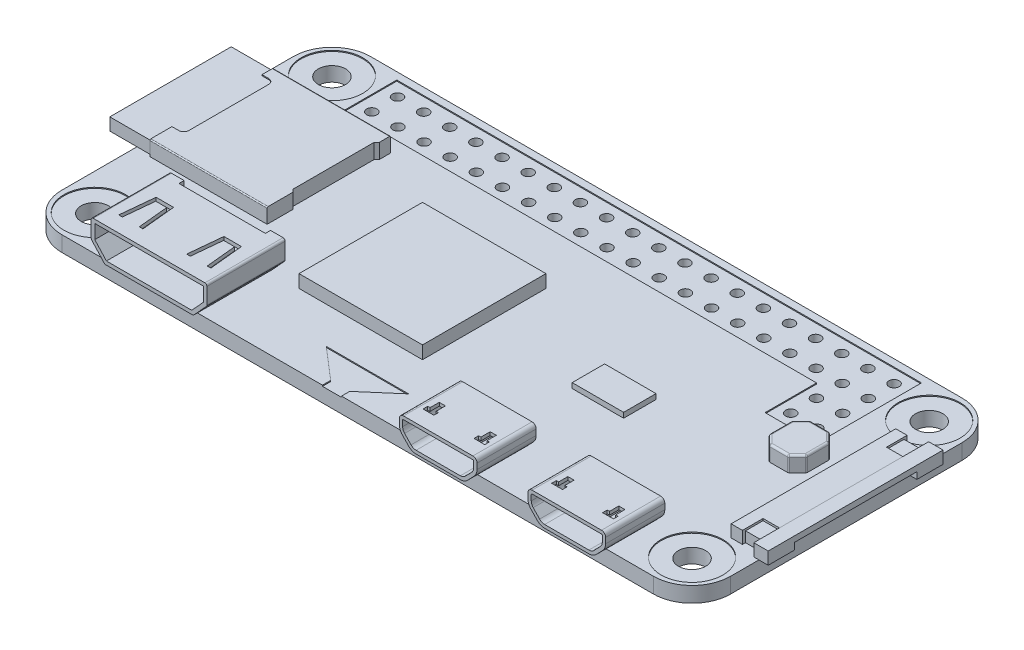
SolidWorks part; units mm, degrees
ref_plane "Front Plane" through (0, 0, 0) normal (0, 0, 1) x (1, 0, 0)
ref_plane "Top Plane" through (0, 0, 0) normal (0, 1, 0) x (1, 0, 0)
ref_plane "Right Plane" through (0, 0, 0) normal (1, 0, 0) x (0, 0, -1)
sketch "Sketch1" plane through (0, 0, 0) normal (0, 1, 0) x (1, 0, 0)
  line L1 (-28.75, 15) -> (28.75, 15)
  line L2 (-32.5, 11.25) -> (-32.5, -11.25)
  line L3 (-28.75, -15) -> (28.75, -15)
  line L4 (32.5, 11.25) -> (32.5, -11.25)
  line L5 (-32.5, 15) -> (32.5, -15) construction
  line L6 (-32.5, -15) -> (32.5, 15) construction
  arc A0 (-32.5, -11.25) -> (-28.75, -15) centre (-28.75, -11.25) ccw
  arc A1 (28.75, -15) -> (32.5, -11.25) centre (28.75, -11.25) ccw
  arc A2 (28.75, 15) -> (32.5, 11.25) centre (28.75, 11.25) cw
  arc A3 (-28.75, 15) -> (-32.5, 11.25) centre (-28.75, 11.25) ccw
  point P0 (0, 0)
  dimension "D3" = 3.75
  dimension "D1" = 65
  dimension "D2" = 30
extrude "Boss-Extrude1" add sketch "Sketch1" along normal blind 1.5 contours L1 A2 L4 A1 L3 A0 L2 A3
sketch "Sketch2" plane through (0, 1.5, 0) normal (0, 1, 0) x (1, 0, 0)
  line L0 (0, 15) -> (0, -15) construction
  line L1 (-28.75, 15) -> (28.75, 15) construction
  line L2 (-28.75, -15) -> (28.75, -15) construction
  line L3 (-32.5, 0) -> (32.5, 0) construction
  line L4 (-32.5, 11.25) -> (-32.5, -11.25) construction
  line L5 (32.5, 11.25) -> (32.5, -11.25) construction
  circle A0 centre (-29.025, 11.525) radius 1.325
  circle A2 centre (29.025, 11.525) radius 1.325
  circle A3 centre (29.025, -11.525) radius 1.325
  circle A4 centre (-29.025, -11.525) radius 1.325
  dimension "D1" = 2.65
  dimension "D2" = 2.15
  dimension "D3" = 2.15
extrude "Cut-Extrude1" cut sketch "Sketch2" against normal through all
sketch "Sketch3" plane through (0, 1.5, 0) normal (0, 1, 0) x (1, 0, 0)
  line L0 (-24.128, 13) -> (-24.128, 10.5) construction
  line L3 (-28.75, 15) -> (28.75, 15) construction
  line L5 (-32.5, 11.25) -> (-32.5, -11.25) construction
  circle A0 centre (-24.128, 13) radius 0.5
  circle A1 centre (-24.128, 10.5) radius 0.5
  dimension "D1" = 1
  dimension "D3" = 1.5
  dimension "D4" = 7.872
  dimension "D2" = 2.5
extrude "Cut-Extrude2" cut sketch "Sketch3" against normal through all
pattern_linear "LPattern1" count 20 spacing 2.54 along (1, 0, 0) of "Cut-Extrude2"
sketch "Sketch5" plane through (0, 1.5, 0) normal (0, 1, 0) x (1, 0, 0)
  line L0 (21.592, 10.5) -> (21.592, 5.5) construction
  line L1 (24.132, 10.5) -> (24.132, 5.5) construction
  line L2 (24.132, 5.5) -> (21.592, 5.5) construction
  circle A0 centre (21.592, 5.5) radius 0.5
  circle A1 centre (24.132, 5.5) radius 0.5
  circle A2 centre (21.592, 8) radius 0.5
  circle A3 centre (24.132, 8) radius 0.5
  dimension "D1" = 2.5
  dimension "D2" = 1
extrude "Cut-Extrude4" cut sketch "Sketch5" against normal through all
sketch "Sketch4" plane through (0, 1.5, 0) normal (0, 1, 0) x (1, 0, 0)
  line L0 (0, 0) -> (0, 14.3) construction
  line L1 (-24.128, 13) -> (-24.128, 10.5) construction
  line L2 (-25.5, 14.3) -> (25.5, 14.3)
  line L3 (-25.5, 14.3) -> (-25.5, 9.2)
  line L4 (-25.5, 9.2) -> (20.4, 9.2)
  line L5 (25.5, 14.3) -> (25.5, 9.2)
  line L6 (-25.5, 11.75) -> (-24.128, 11.75) construction
  line L7 (20.4, 9.2) -> (25.5, 9.2) construction
  line L8 (-2.5, -15) -> (-2.5, -11.55) construction
  line L9 (25.5, 9.2) -> (25.5, 4.2)
  line L10 (25.5, 4.2) -> (20.4, 4.2)
  line L11 (20.4, 9.2) -> (20.4, 4.2)
  line L12 (-28.75, -15) -> (28.75, -15) construction
  line L13 (-6.5, -11.55) -> (1.5, -11.55)
  line L14 (1.5, -11.55) -> (-1.575, -14.2)
  line L15 (-1.575, -14.2) -> (-1.575, -15)
  line L16 (-1.575, -15) -> (-3.425, -15)
  line L17 (-3.425, -15) -> (-3.425, -14.2)
  line L18 (-3.425, -14.2) -> (-6.5, -11.55)
  line L19 (-32.5, 11.25) -> (-32.5, -11.25) construction
  circle A0 centre (-29.025, 11.525) radius 3
  circle A1 centre (-29.025, -11.525) radius 3
  circle A2 centre (29.025, -11.525) radius 3
  circle A3 centre (29.025, 11.525) radius 3
  point P23 (-24.128, 11.75)
  point P26 (-25.5, 11.75)
  dimension "D1" = 6
  dimension "D2" = 5.1
  dimension "D3" = 51
  dimension "D4" = 5.1
  dimension "D5" = 5
  dimension "D6" = 8
  dimension "D7" = 1.85
  dimension "D8" = 3.45
  dimension "D9" = 0.8
  dimension "D10" = 30
extrude "Cut-Extrude3" cut sketch "Sketch4" against normal blind 0.1
sketch "Sketch6" plane through (0, 1.5, 0) normal (0, 1, 0) x (1, 0, 0)
  line L0 (-28.75, -15) -> (-3.425, -15) construction
  line L1 (-12.7, 4) -> (-0.7, 4)
  line L2 (-12.7, 4) -> (-12.7, -8)
  line L3 (-12.7, -8) -> (-0.7, -8)
  line L4 (-0.7, 4) -> (-0.7, -8)
  line L5 (-12.7, 4) -> (-0.7, -8) construction
  line L6 (-12.7, -8) -> (-0.7, 4) construction
  line L7 (-32.5, 11.25) -> (-32.5, -11.25) construction
  point P0 (-6.7, -2)
  dimension "D1" = 12
  dimension "D2" = 7
  dimension "D3" = 19.8
extrude "Boss-Extrude2" add sketch "Sketch6" along normal blind 1.25
sketch "Sketch7" plane through (0, 1.5, 0) normal (0, 1, 0) x (1, 0, 0)
  line L0 (-19.65, 7.85) -> (-19.65, 6.75)
  line L1 (-31.05, 7.85) -> (-19.65, 7.85)
  line L2 (-31.05, 7.85) -> (-31.05, -4.15) construction
  line L3 (-31.05, -4.15) -> (-19.65, -4.15)
  line L4 (-19.65, 7.85) -> (-19.65, -4.15) construction
  line L5 (-19.65, 6.75) -> (-19.9, 6.5)
  line L6 (-19.9, 6.5) -> (-19.9, -1.4)
  line L7 (-19.9, -1.4) -> (-19.65, -1.65)
  line L8 (-19.65, -1.65) -> (-19.65, -4.15)
  line L9 (-31.05, 7.85) -> (-31.05, 6.75)
  line L10 (-31.05, 6.75) -> (-30.4, 6.75)
  line L11 (-29.9, 6.25) -> (-29.9, -1.5)
  line L12 (-30.4, -2) -> (-31.05, -2)
  line L13 (-31.05, -2) -> (-31.05, -4.15)
  line L14 (-28.75, 15) -> (28.75, 15) construction
  line L15 (-32.5, 11.25) -> (-32.5, -11.25) construction
  arc A0 (-29.9, -1.5) -> (-30.4, -2) centre (-30.4, -1.5) cw
  arc A1 (-30.4, 6.75) -> (-29.9, 6.25) centre (-30.4, 6.25) cw
  dimension "D9" = 0.5
  dimension "D1" = 11.4
  dimension "D2" = 12
  dimension "D3" = 2.5
  dimension "D4" = 1.1
  dimension "D5" = 0.25
  dimension "D6" = 1.1
  dimension "D7" = 2.15
  dimension "D8" = 1.15
  dimension "D10" = 7.15
  dimension "D11" = 1.45
extrude "Boss-Extrude3" add sketch "Sketch7" along normal blind 1.45
fillet "Fillet2" radius 0.1 2 edges at (-25.35, 2.95, -7.85) (-25.35, 2.95, 4.15)
sketch "Sketch8" plane through (-29.9, 0, 0) normal (-1, 0, 0) x (0, 0, 1)
  line L0 (-7.85, 2.85) -> (-7.85, 1.5) construction
  line L1 (-7.75, 2.85) -> (4.05, 2.85)
  line L2 (-7.75, 2.85) -> (-7.75, 1.6)
  line L3 (-7.75, 1.6) -> (4.05, 1.6)
  line L4 (4.05, 2.85) -> (4.05, 1.6)
  line L5 (-6.25, 2.95) -> (1.5, 2.95) construction
  line L6 (4.15, 2.85) -> (4.15, 1.5) construction
  line L7 (-6.25, 1.5) -> (1.5, 1.5) construction
  dimension "D1" = 0.1
  dimension "D2" = 0.1
  dimension "D3" = 0.1
  dimension "D4" = 0.1
extrude "Cut-Extrude5" cut sketch "Sketch8" against normal blind 9.5 and the other way through all
sketch "Sketch9" plane through (0, 0, 15) normal (0, 0, 1) x (1, 0, 0)
  line L0 (-19.875, 1.5) -> (-19.875, 4.8) construction
  line L1 (-28.75, 1.5) -> (-3.425, 1.5) construction
  line L2 (-25.5, 4.8) -> (-14.25, 4.8)
  line L3 (-14.25, 4.8) -> (-14.25, 2.95)
  line L4 (-14.25, 2.95) -> (-15.575, 1.5)
  line L5 (-12.7, 1.5) -> (-0.7, 1.5) construction
  line L6 (-15.575, 1.5) -> (-24.175, 1.5)
  line L7 (-24.175, 1.5) -> (-25.5, 2.95)
  line L8 (-25.5, 2.95) -> (-25.5, 4.8)
  line L9 (-32.5, 1.5) -> (-32.5, 0) construction
  dimension "D1" = 3.3
  dimension "D2" = 1.85
  dimension "D3" = 8.6
  dimension "D4" = 11.25
  dimension "D5" = 7
extrude "Boss-Extrude4" add sketch "Sketch9" along normal blind 0.4 and the other way blind 7.2 separate body
fillet "Fillet1" radius 0.2 6 edges at (-15.575, 1.5, 11.6) (-24.175, 1.5, 11.6) (-25.5, 2.95, 11.6) (-14.25, 2.95, 11.6) (-25.5, 4.8, 11.6) (-14.25, 4.8, 11.6)
sketch "Sketch10" plane through (0, 0, 15.4) normal (0, 0, 1) x (1, 0, 0)
  line L12 (-25.15, 4.45) -> (-25.15, 3.0858)
  line L13 (-25.15, 3.0858) -> (-24.0207, 1.85)
  line L14 (-24.0207, 1.85) -> (-15.7293, 1.85)
  line L15 (-15.7293, 1.85) -> (-14.6, 3.0858)
  line L16 (-14.6, 3.0858) -> (-14.6, 4.45)
  line L17 (-14.6, 4.45) -> (-25.15, 4.45)
  line L18 (-25.15, 4.45) -> (-25.15, 3.0858)
  line L19 (-25.15, 3.0858) -> (-24.0207, 1.85)
  line L20 (-24.0207, 1.85) -> (-15.7293, 1.85)
  line L21 (-15.7293, 1.85) -> (-14.6, 3.0858)
  line L22 (-14.6, 3.0858) -> (-14.6, 4.45)
  line L23 (-14.6, 4.45) -> (-25.15, 4.45)
  dimension "D1" = 0.35
extrude "Cut-Extrude6" cut sketch "Sketch10" against normal blind 7
sketch "Sketch11" plane through (0, 0, 8.4) normal (0, 0, 1) x (1, 0, 0)
  line L0 (-19.875, 3.6) -> (-19.875, 1.85) construction
  line L1 (-23.375, 3.05) -> (-16.375, 3.05)
  line L2 (-23.375, 3.05) -> (-23.375, 3.6)
  line L3 (-23.375, 3.6) -> (-16.375, 3.6)
  line L4 (-16.375, 3.05) -> (-16.375, 3.6)
  line L5 (-24.0207, 1.85) -> (-15.7293, 1.85) construction
  line L6 (-24.0207, 1.85) -> (-15.7293, 1.85) construction
  dimension "D1" = 7
  dimension "D2" = 0.55
  dimension "D3" = 1.2
extrude "Boss-Extrude5" add sketch "Sketch11" along normal blind 3.5
sketch "Sketch12" plane through (0, 4.45, 0) normal (0, -1, 0) x (1, 0, 0)
  line L0 (-19.875, 7.8) -> (-19.875, 15.4) construction
  line L1 (-14.45, 7.8) -> (-25.3, 7.8) construction
  line L2 (-14.45, 15.4) -> (-25.3, 15.4) construction
  line L3 (-23.175, 10.57) -> (-23.175, 13.4458) construction
  line L4 (-24.025, 10.57) -> (-22.325, 10.57)
  line L5 (-22.325, 10.57) -> (-22, 13.87)
  line L6 (-22, 13.87) -> (-22.3517, 13.87)
  line L7 (-22.3517, 13.87) -> (-22.6422, 10.92)
  line L8 (-22.6422, 10.92) -> (-23.7078, 10.92)
  line L9 (-23.9983, 13.87) -> (-23.7078, 10.92)
  line L10 (-24.35, 13.87) -> (-23.9983, 13.87)
  line L11 (-24.025, 10.57) -> (-24.35, 13.87)
  line L12 (-16.575, 10.57) -> (-16.575, 13.4458) construction
  line L13 (-15.725, 10.57) -> (-15.4, 13.87)
  line L14 (-15.4, 13.87) -> (-15.7517, 13.87)
  line L15 (-15.7517, 13.87) -> (-16.0422, 10.92)
  line L16 (-17.1078, 10.92) -> (-16.0422, 10.92)
  line L17 (-17.3983, 13.87) -> (-17.1078, 10.92)
  line L18 (-17.75, 13.87) -> (-17.3983, 13.87)
  line L19 (-17.425, 10.57) -> (-17.75, 13.87)
  line L20 (-15.725, 10.57) -> (-17.425, 10.57)
  point P15 (-23.175, 10.92)
  point P28 (-16.575, 10.92)
  dimension "D1" = 0.35
  dimension "D2" = 0.35
  dimension "D3" = 3.3
  dimension "D4" = 2.35
  dimension "D5" = 1.7
  dimension "D6" = 2.77
  dimension "D7" = 4.25
extrude "Cut-Extrude7" cut sketch "Sketch12" against normal through all
sketch "Sketch13" plane through (0, 0, 7.8) normal (0, 0, -1) x (-1, 0, 0)
  line L0 (14.45, 4.8) -> (25.3, 4.8) construction
  line L1 (15.675, 4.8) -> (24.075, 4.8)
  line L2 (15.675, 4.8) -> (15.675, 3.4)
  line L3 (15.675, 3.4) -> (24.075, 3.4)
  line L4 (24.075, 4.8) -> (24.075, 3.4)
  line L5 (19.875, 1.5) -> (19.875, 4.8) construction
  line L6 (24.0868, 1.5) -> (15.6632, 1.5) construction
  dimension "D1" = 8.4
  dimension "D2" = 1.4
extrude "Cut-Extrude8" cut sketch "Sketch13" against normal blind 0.5
sketch "Sketch15" plane through (0, 0, 15) normal (0, 0, 1) x (1, 0, 0)
  line L0 (21.575, 1.5) -> (21.575, 4.1) construction
  line L1 (-1.575, 1.5) -> (28.75, 1.5) construction
  line L2 (18.2, 4.1) -> (24.95, 4.1)
  line L3 (25.35, 3.7) -> (25.35, 3.1523)
  line L4 (25.0714, 2.4598) -> (24.4452, 1.8075)
  line L5 (23.7238, 1.5) -> (19.4262, 1.5)
  line L6 (32.5, 1.5) -> (32.5, 0) construction
  line L7 (18.0786, 2.4598) -> (18.7048, 1.8075)
  line L8 (17.8, 3.7) -> (17.8, 3.1523)
  line L9 (15.325, 0) -> (15.325, 5.5788) construction
  line L10 (-28.75, 0) -> (28.75, 0) construction
  line L11 (9.075, 1.5) -> (9.075, 4.1) construction
  line L12 (12.85, 3.7) -> (12.85, 3.1523)
  line L13 (12.5714, 2.4598) -> (11.9452, 1.8075)
  line L14 (6.9262, 1.5) -> (11.2238, 1.5)
  line L15 (5.5786, 2.4598) -> (6.2048, 1.8075)
  line L16 (5.3, 3.7) -> (5.3, 3.1523)
  line L17 (12.45, 4.1) -> (5.7, 4.1)
  arc A0 (24.4452, 1.8075) -> (23.7238, 1.5) centre (23.7238, 2.5) cw
  arc A1 (18.7048, 1.8075) -> (19.4262, 1.5) centre (19.4262, 2.5) ccw
  arc A2 (25.35, 3.1523) -> (25.0714, 2.4598) centre (24.35, 3.1523) cw
  arc A3 (18.0786, 2.4598) -> (17.8, 3.1523) centre (18.8, 3.1523) cw
  arc A4 (24.95, 4.1) -> (25.35, 3.7) centre (24.95, 3.7) cw
  arc A5 (17.8, 3.7) -> (18.2, 4.1) centre (18.2, 3.7) cw
  arc A6 (12.85, 3.7) -> (12.45, 4.1) centre (12.45, 3.7) ccw
  arc A7 (5.7, 4.1) -> (5.3, 3.7) centre (5.7, 3.7) ccw
  arc A8 (12.5714, 2.4598) -> (12.85, 3.1523) centre (11.85, 3.1523) ccw
  arc A9 (5.3, 3.1523) -> (5.5786, 2.4598) centre (6.3, 3.1523) ccw
  arc A10 (11.9452, 1.8075) -> (11.2238, 1.5) centre (11.2238, 2.5) cw
  arc A11 (6.2048, 1.8075) -> (6.9262, 1.5) centre (6.9262, 2.5) ccw
  point P14 (24.15, 1.5)
  point P17 (19, 1.5)
  point P20 (25.35, 2.75)
  point P23 (17.8, 2.75)
  point P26 (25.35, 4.1)
  point P29 (17.8, 4.1)
  point P54 (12.85, 4.1)
  point P55 (5.3, 4.1)
  point P56 (12.85, 2.75)
  point P57 (5.3, 2.75)
  point P58 (11.65, 1.5)
  point P59 (6.5, 1.5)
  dimension "D6" = 1
  dimension "D7" = 0.4
  dimension "D1" = 7.55
  dimension "D2" = 2.6
  dimension "D3" = 1.35
  dimension "D4" = 5.15
  dimension "D5" = 7.15
  dimension "D8" = 4.95
extrude "Boss-Extrude6" add sketch "Sketch15" along normal blind 1.25 and the other way blind 4.5
sketch "Sketch16" plane through (0, 0, 16.25) normal (0, 0, 1) x (1, 0, 0)
  line L12 (12.45, 3.78) -> (5.7, 3.78)
  line L13 (5.62, 3.7) -> (5.62, 3.1523)
  line L14 (5.8095, 2.6814) -> (6.4357, 2.0291)
  line L15 (6.9262, 1.82) -> (11.2238, 1.82)
  line L16 (11.7143, 2.0291) -> (12.3405, 2.6814)
  line L17 (12.53, 3.1523) -> (12.53, 3.7)
  line L18 (12.45, 3.78) -> (5.7, 3.78)
  line L19 (5.62, 3.7) -> (5.62, 3.1523)
  line L20 (5.8095, 2.6814) -> (6.4357, 2.0291)
  line L21 (6.9262, 1.82) -> (11.2238, 1.82)
  line L22 (11.7143, 2.0291) -> (12.3405, 2.6814)
  line L23 (12.53, 3.1523) -> (12.53, 3.7)
  line L30 (24.2143, 2.0291) -> (24.8405, 2.6814)
  line L31 (25.03, 3.1523) -> (25.03, 3.7)
  line L32 (24.95, 3.78) -> (18.2, 3.78)
  line L33 (18.12, 3.7) -> (18.12, 3.1523)
  line L34 (18.3095, 2.6814) -> (18.9357, 2.0291)
  line L35 (19.4262, 1.82) -> (23.7238, 1.82)
  line L36 (24.2143, 2.0291) -> (24.8405, 2.6814)
  line L37 (25.03, 3.1523) -> (25.03, 3.7)
  line L38 (24.95, 3.78) -> (18.2, 3.78)
  line L39 (18.12, 3.7) -> (18.12, 3.1523)
  line L40 (18.3095, 2.6814) -> (18.9357, 2.0291)
  line L41 (19.4262, 1.82) -> (23.7238, 1.82)
  arc A12 (12.53, 3.7) -> (12.45, 3.78) centre (12.45, 3.7) ccw
  arc A13 (5.7, 3.78) -> (5.62, 3.7) centre (5.7, 3.7) ccw
  arc A14 (5.62, 3.1523) -> (5.8095, 2.6814) centre (6.3, 3.1523) ccw
  arc A15 (6.4357, 2.0291) -> (6.9262, 1.82) centre (6.9262, 2.5) ccw
  arc A16 (11.2238, 1.82) -> (11.7143, 2.0291) centre (11.2238, 2.5) ccw
  arc A17 (12.3405, 2.6814) -> (12.53, 3.1523) centre (11.85, 3.1523) ccw
  arc A18 (12.53, 3.7) -> (12.45, 3.78) centre (12.45, 3.7) ccw
  arc A19 (5.7, 3.78) -> (5.62, 3.7) centre (5.7, 3.7) ccw
  arc A20 (5.62, 3.1523) -> (5.8095, 2.6814) centre (6.3, 3.1523) ccw
  arc A21 (6.4357, 2.0291) -> (6.9262, 1.82) centre (6.9262, 2.5) ccw
  arc A22 (11.2238, 1.82) -> (11.7143, 2.0291) centre (11.2238, 2.5) ccw
  arc A23 (12.3405, 2.6814) -> (12.53, 3.1523) centre (11.85, 3.1523) ccw
  arc A30 (23.7238, 1.82) -> (24.2143, 2.0291) centre (23.7238, 2.5) ccw
  arc A31 (24.8405, 2.6814) -> (25.03, 3.1523) centre (24.35, 3.1523) ccw
  arc A32 (25.03, 3.7) -> (24.95, 3.78) centre (24.95, 3.7) ccw
  arc A33 (18.2, 3.78) -> (18.12, 3.7) centre (18.2, 3.7) ccw
  arc A34 (18.12, 3.1523) -> (18.3095, 2.6814) centre (18.8, 3.1523) ccw
  arc A35 (18.9357, 2.0291) -> (19.4262, 1.82) centre (19.4262, 2.5) ccw
  arc A36 (23.7238, 1.82) -> (24.2143, 2.0291) centre (23.7238, 2.5) ccw
  arc A37 (24.8405, 2.6814) -> (25.03, 3.1523) centre (24.35, 3.1523) ccw
  arc A38 (25.03, 3.7) -> (24.95, 3.78) centre (24.95, 3.7) ccw
  arc A39 (18.2, 3.78) -> (18.12, 3.7) centre (18.2, 3.7) ccw
  arc A40 (18.12, 3.1523) -> (18.3095, 2.6814) centre (18.8, 3.1523) ccw
  arc A41 (18.9357, 2.0291) -> (19.4262, 1.82) centre (19.4262, 2.5) ccw
  dimension "D1" = 0.32
  dimension "D2" = 0.32
extrude "Cut-Extrude9" cut sketch "Sketch16" against normal blind 5.25
sketch "Sketch17" plane through (0, 0, 11) normal (0, 0, 1) x (1, 0, 0)
  line L0 (12.85, 3.4262) -> (17.8, 3.4262) construction
  line L1 (12.85, 3.1523) -> (12.85, 3.7) construction
  line L2 (17.8, 3.7) -> (17.8, 3.1523) construction
  line L3 (15.325, 3.4262) -> (15.325, 1.5) construction
  line L4 (11.2238, 1.5) -> (19.4262, 1.5) construction
  line L5 (9.075, 1.82) -> (9.075, 3.78) construction
  line L6 (6.9262, 1.82) -> (11.2238, 1.82) construction
  line L7 (12.45, 3.78) -> (5.7, 3.78) construction
  line L8 (6.9262, 1.82) -> (11.2238, 1.82) construction
  line L9 (7.5, 3.42) -> (10.65, 3.42)
  line L10 (7.5, 3.42) -> (7.5, 3.02)
  line L11 (7.5, 3.02) -> (10.65, 3.02)
  line L12 (10.65, 3.42) -> (10.65, 3.02)
  line L13 (7.5, 3.42) -> (10.65, 3.02) construction
  line L14 (7.5, 3.02) -> (10.65, 3.42) construction
  line L15 (23.15, 3.02) -> (20, 3.42) construction
  line L16 (23.15, 3.42) -> (20, 3.02) construction
  line L17 (20, 3.42) -> (20, 3.02)
  line L18 (23.15, 3.02) -> (20, 3.02)
  line L19 (23.15, 3.42) -> (23.15, 3.02)
  line L20 (23.15, 3.42) -> (20, 3.42)
  point P16 (9.075, 3.22)
  point P27 (21.575, 3.22)
  dimension "D1" = 3.15
  dimension "D2" = 0.4
  dimension "D3" = 1.4
extrude "Boss-Extrude7" add sketch "Sketch17" along normal blind 3.5
sketch "Sketch18" plane through (0, 4.1, 0) normal (0, 1, 0) x (1, 0, 0)
  line L0 (9.075, -16.25) -> (9.075, -10.5) construction
  line L1 (12.45, -16.25) -> (5.7, -16.25) construction
  line L2 (6.9262, -10.5) -> (11.2238, -10.5) construction
  line L3 (12.85, -16.25) -> (17.8, -16.25) construction
  line L4 (15.325, -16.25) -> (15.325, -10.5) construction
  line L5 (6.6, -13.37) -> (6.6, -14.72) construction
  line L6 (6.9, -13.37) -> (6.3, -13.37)
  line L7 (6.3, -13.37) -> (6.3, -14.27)
  line L8 (6.3, -14.27) -> (6.075, -14.27)
  line L9 (6.075, -14.27) -> (6.075, -14.72)
  line L10 (6.075, -14.72) -> (7.125, -14.72)
  line L11 (7.125, -14.27) -> (7.125, -14.72)
  line L12 (6.9, -14.27) -> (7.125, -14.27)
  line L13 (6.9, -13.37) -> (6.9, -14.27)
  line L14 (11.55, -13.37) -> (11.55, -14.72) construction
  line L15 (11.25, -13.37) -> (11.25, -14.27)
  line L16 (11.25, -14.27) -> (11.025, -14.27)
  line L17 (11.025, -14.27) -> (11.025, -14.72)
  line L18 (12.075, -14.72) -> (11.025, -14.72)
  line L19 (12.075, -14.27) -> (12.075, -14.72)
  line L20 (11.85, -14.27) -> (12.075, -14.27)
  line L21 (11.85, -13.37) -> (11.85, -14.27)
  line L22 (11.25, -13.37) -> (11.85, -13.37)
  line L23 (19.1, -13.37) -> (19.1, -14.72) construction
  line L24 (24.05, -13.37) -> (24.05, -14.72) construction
  line L25 (21.575, -16.25) -> (21.575, -10.5) construction
  line L26 (19.4, -13.37) -> (18.8, -13.37)
  line L27 (18.8, -13.37) -> (18.8, -14.27)
  line L28 (18.8, -14.27) -> (18.575, -14.27)
  line L29 (18.575, -14.27) -> (18.575, -14.72)
  line L30 (18.575, -14.72) -> (19.625, -14.72)
  line L31 (19.625, -14.27) -> (19.625, -14.72)
  line L32 (19.4, -14.27) -> (19.625, -14.27)
  line L33 (19.4, -13.37) -> (19.4, -14.27)
  line L34 (23.75, -13.37) -> (23.75, -14.27)
  line L35 (23.75, -14.27) -> (23.525, -14.27)
  line L36 (23.525, -14.27) -> (23.525, -14.72)
  line L37 (24.575, -14.72) -> (23.525, -14.72)
  line L38 (24.575, -14.27) -> (24.575, -14.72)
  line L39 (24.35, -14.27) -> (24.575, -14.27)
  line L40 (24.35, -13.37) -> (24.35, -14.27)
  line L41 (23.75, -13.37) -> (24.35, -13.37)
  dimension "D1" = 1.05
  dimension "D2" = 1.35
  dimension "D3" = 0.9
  dimension "D4" = 0.6
  dimension "D5" = 3.9
  dimension "D6" = 1.53
extrude "Cut-Extrude10" cut sketch "Sketch18" against normal up to surface (0.32 mm away) up to face at (9.075, 3.78, 13.625)
sketch "Sketch19" plane through (32.5, 0, 0) normal (1, 0, 0) x (0, 0, -1)
  line L0 (0, 1.5) -> (0, 2.7) construction
  line L1 (11.25, 1.5) -> (-11.25, 1.5) construction
  line L2 (-8.5, 2.7) -> (8.5, 2.7)
  line L3 (8.5, 2.7) -> (8.5, 1.5)
  line L4 (6.5, 1.5) -> (6.75, 1.5) construction
  line L5 (8.5, 1.5) -> (5.95, 1.5)
  line L6 (-1.4, 1.5) -> (6.5, 1.5) construction
  line L7 (5.95, 1.5) -> (5.95, 2.15)
  line L8 (5.95, 2.15) -> (-5.95, 2.15)
  line L9 (-5.95, 2.15) -> (-5.95, 1.5)
  line L10 (-5.95, 1.5) -> (-8.5, 1.5)
  line L11 (-8, 1.5) -> (4, 1.5) construction
  line L12 (-8.5, 1.5) -> (-8.5, 2.7)
  line L13 (15, 1.5) -> (15, 0) construction
  dimension "D1" = 1.2
  dimension "D2" = 0.55
  dimension "D3" = 11.9
  dimension "D4" = 17
  dimension "D5" = 6.5
extrude "Boss-Extrude8" add sketch "Sketch19" along normal blind 0.9 and the other way blind 0.5
sketch "Sketch20" plane through (0, 1.5, 0) normal (0, 1, 0) x (1, 0, 0)
  line L0 (33.4, 0) -> (29.3, 0) construction
  line L1 (33.4, 8.5) -> (33.4, -8.5) construction
  line L2 (32, 6) -> (30.4, 6)
  line L3 (32, 8.5) -> (32, -8.5) construction
  line L4 (30.4, 6) -> (30.4, 8)
  line L5 (30.4, 8) -> (29.3, 8)
  line L6 (29.3, 8) -> (29.3, -8)
  line L7 (29.3, -8) -> (30.4, -8)
  line L8 (30.4, -8) -> (30.4, -6)
  line L9 (30.4, -6) -> (32, -6)
  line L10 (32, -6) -> (32, 6)
  dimension "D1" = 16
  dimension "D2" = 2.7
  dimension "D3" = 1.1
  dimension "D4" = 12
extrude "Boss-Extrude9" add sketch "Sketch20" along normal blind 1.19
sketch "Sketch21" plane through (0, 1.5, 0) normal (0, 1, 0) x (1, 0, 0)
  line L0 (32, 6) -> (32, 8.5) construction
  line L1 (30.4, 6) -> (32, 6)
  line L2 (30.4, 6) -> (30.4, 7.7)
  line L3 (30.4, 7.7) -> (32, 7.7)
  line L4 (32, 6) -> (32, 7.7)
  line L5 (32, 8.5) -> (32, -8.5) construction
  line L6 (30.4, -6) -> (32, -6)
  line L7 (30.4, -6) -> (30.4, -7.7)
  line L8 (30.4, -7.7) -> (32, -7.7)
  line L9 (32, -6) -> (32, -7.7)
  dimension "D1" = 1.7
extrude "Boss-Extrude10" add sketch "Sketch21" along normal blind 1
sketch "Sketch22" plane through (0, 1.5, 0) normal (0, 1, 0) x (1, 0, 0)
  line L0 (32.5, -8.5) -> (32.5, -11.25) construction
  line L1 (23.85, 4.25) -> (27.5, 4.25)
  line L2 (23.85, 4.25) -> (23.85, 0.25)
  line L3 (23.85, 0.25) -> (27.5, 0.25)
  line L4 (27.5, 4.25) -> (27.5, 0.25)
  line L5 (-28.75, 15) -> (28.75, 15) construction
  dimension "D1" = 3.65
  dimension "D2" = 4
  dimension "D3" = 5
  dimension "D4" = 10.75
extrude "Boss-Extrude11" add sketch "Sketch22" along normal blind 1.5
chamfer "Chamfer1" distance 0.9 angle 45 4 edges at (23.85, 2.25, -4.25) (27.5, 2.25, -4.25) (27.5, 2.25, -0.25) (23.85, 2.25, -0.25)
sketch "Sketch23" plane through (0, 1.5, 0) normal (0, 1, 0) x (1, 0, 0)
  line L0 (-28.75, 15) -> (28.75, 15) construction
  line L1 (9, 0) -> (14, 0)
  line L2 (9, 0) -> (9, -3.15)
  line L3 (9, -3.15) -> (14, -3.15)
  line L4 (14, 0) -> (14, -3.15)
  line L5 (32.5, -8.5) -> (32.5, -11.25) construction
  dimension "D1" = 5
  dimension "D2" = 3.15
  dimension "D3" = 15
  dimension "D4" = 18.5
extrude "Boss-Extrude12" add sketch "Sketch23" along normal blind 0.5
fillet "Fillet3" radius 0.2 16 edges at (27.05, 3, -3.8) (27.5, 3, -2.25) (27.05, 3, -0.7) (25.675, 3, -0.25) (24.3, 3, -0.7) (23.85, 3, -2.25) (24.3, 3, -3.8) (25.675, 3, -4.25) (26.6, 2.25, -4.25) (24.75, 2.25, -4.25) (23.85, 2.25, -3.35) (24.75, 2.25, -0.25) (23.85, 2.25, -1.15) (27.5, 2.25, -3.35) (27.5, 2.25, -1.15) (26.6, 2.25, -0.25)
sketch "Sketch24" plane through (0, 1.6, 0) normal (0, 1, 0) x (1, 0, 0)
  line L0 (-19.65, 7.75) -> (-31.05, 7.75) construction
  line L1 (-20, 7.75) -> (-35.04, 7.75)
  line L2 (-20, 7.75) -> (-20, -4.05)
  line L3 (-20, -4.05) -> (-35.04, -4.05)
  line L4 (-35.04, 7.75) -> (-35.04, -4.05)
  line L5 (-31.05, -4.05) -> (-19.65, -4.05) construction
  line L7 (-19.9, -1.4) -> (-19.9, 6.5) construction
  line L8 (-32.5, 11.25) -> (-32.5, -11.25) construction
  point P8 (-38.6449, -4.05)
  dimension "D1" = 0.1
  dimension "D2" = 2.54
extrude "Boss-Extrude13" add sketch "Sketch24" along normal blind 1.2
